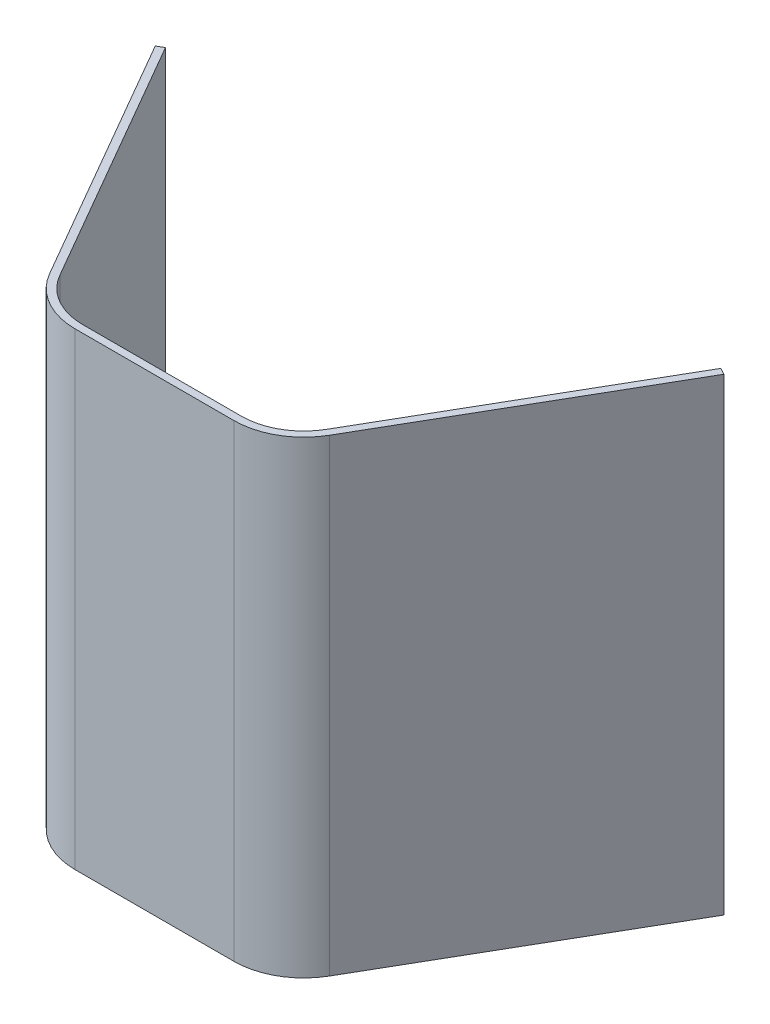
SolidWorks part; units mm, degrees
ref_plane "Plan de face" through (0, 0, 0) normal (0, 0, 1) x (1, 0, 0)
ref_plane "Plan de dessus" through (0, 0, 0) normal (0, 1, 0) x (1, 0, 0)
ref_plane "Plan de droite" through (0, 0, 0) normal (1, 0, 0) x (0, 0, -1)
sketch "Esquisse1" plane through (0, 0, 0) normal (0, 1, 0) x (1, 0, 0)
  line L0 (-45.5186, 77.6406) -> (-22.4012, 37.6)
  line L1 (-12.7017, 32) -> (12.7017, 32)
  line L2 (22.4012, 37.6) -> (45.5186, 77.6406)
  line L3 (0, -13.8682) -> (0, 114.7954) construction
  line L4 (0, 0) -> (-60.2437, 104.3452) construction
  line L5 (-44.4794, 78.2406) -> (-21.362, 38.2)
  line L6 (-12.7017, 33.2) -> (12.7017, 33.2)
  line L7 (21.362, 38.2) -> (44.4794, 78.2406)
  line L8 (-45.5186, 77.6406) -> (-44.4794, 78.2406)
  line L9 (45.5186, 77.6406) -> (44.4794, 78.2406)
  line L10 (-18.4752, 33.2) -> (18.4752, 33.2) construction
  line L11 (18.4752, 33.2) -> (44.4794, 78.2406) construction
  line L12 (-44.4794, 78.2406) -> (-18.4752, 33.2) construction
  line L13 (-19.168, 32) -> (19.168, 32) construction
  line L14 (19.168, 32) -> (45.5186, 77.6406) construction
  line L15 (-45.5186, 77.6406) -> (-19.168, 32) construction
  arc A0 (12.7017, 33.2) -> (21.362, 38.2) centre (12.7017, 43.2) ccw
  arc A1 (-21.362, 38.2) -> (-12.7017, 33.2) centre (-12.7017, 43.2) ccw
  arc A2 (12.7017, 32) -> (22.4012, 37.6) centre (12.7017, 43.2) ccw
  arc A3 (-22.4012, 37.6) -> (-12.7017, 32) centre (-12.7017, 43.2) ccw
  dimension "D5" = 10
  dimension "D6" = 11.2
  dimension "D1" = 30
  dimension "D3" = 32
  dimension "D4" = 90
  dimension "D2" = 1.2
extrude "Boss.-Extru.1" add sketch "Esquisse1" along normal blind 75
